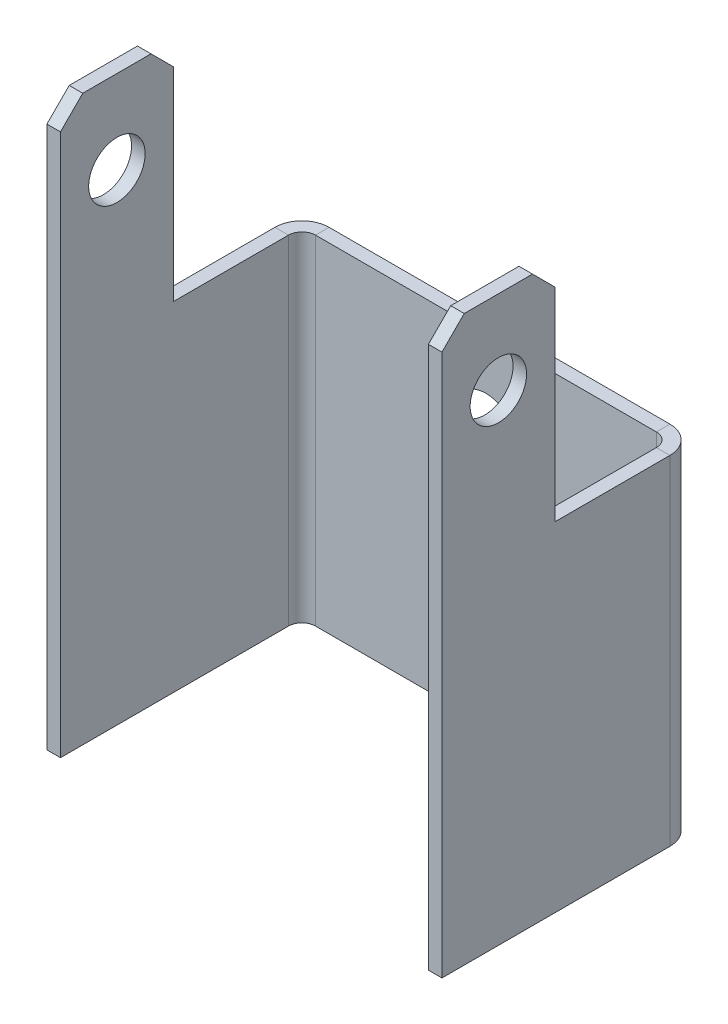
SolidWorks part; units mm, degrees
note: The reader was unsure of these and kept them because the rebuilt part matched: flange length of "Brida de arista1".
ref_plane "Alzado" through (0, 0, 0) normal (0, 0, 1) x (1, 0, 0)
ref_plane "Planta" through (0, 0, 0) normal (0, 1, 0) x (1, 0, 0)
ref_plane "Vista lateral" through (0, 0, 0) normal (1, 0, 0) x (0, 0, -1)
sketch "Croquis1" plane through (0, 0, 0) normal (0, 0, 1) x (1, 0, 0)
  line L1 (-22.225, 31.75) -> (22.225, 31.75)
  line L2 (-22.225, 31.75) -> (-22.225, -31.75)
  line L3 (-22.225, -31.75) -> (22.225, -31.75)
  line L4 (22.225, 31.75) -> (22.225, -31.75)
  line L5 (-22.225, 31.75) -> (22.225, -31.75) construction
  line L6 (-22.225, -31.75) -> (22.225, 31.75) construction
  point P0 (0, 0)
  dimension "D1" = 63.5
  dimension "D2" = 44.45
base flange "Brida base1" sketch "Croquis1" thickness 1.524 reverse thickness direction no parameters "D1"=0.508
edge flange "Brida de arista1" sketch "Croquis10" flange profiles "Croquis10", "Croquis11" flange angle 90 flange length 28.702 flange position material inside bend radius 1.524 thickness 1.524 relief rectangular parameters "D6"=10, "D8"=1
sketch "Croquis10" plane through (22.225, 0, 0) normal (-1, 0, 0) x (0, -1, 0)
  line L2 (-31.75, 0) -> (-31.75, 27.178)
  line L3 (-31.75, 27.178) -> (31.75, 27.178)
  line L4 (31.75, 27.178) -> (31.75, 0)
  line L5 (31.75, 0) -> (-31.75, 0) construction
  line L6 (31.75, 0) -> (-31.75, 0)
sketch "Croquis11" plane through (-22.225, 0, 0) normal (1, 0, 0) x (0, 1, 0)
  line L0 (31.75, 0) -> (-31.75, 0) construction
  line L1 (31.75, 0) -> (-31.75, 0)
  line L2 (31.75, 0) -> (31.75, 27.178)
  line L3 (31.75, 27.178) -> (-31.75, 27.178)
  line L4 (-31.75, 27.178) -> (-31.75, 0)
bend "Pliegue de arista1" bend radius 1.524 bend angle 90 parameters "D5"=1
bend "Pliegue de arista2" bend radius 1.524 bend angle 90 parameters "D5"=2
sketch "Croquis12" plane through (22.225, 0, 0) normal (1, 0, 0) x (0, 0, -1)
  line L0 (-14.478, 31.75) -> (-14.478, 6.35)
  line L4 (-27.178, 31.75) -> (-1.524, 31.75) construction
  line L6 (1.524, 6.35) -> (-14.478, 6.35)
  line L7 (1.524, 31.75) -> (1.524, -31.75) construction
  line L8 (-1.524, -31.75) -> (-27.178, -31.75) construction
  line L11 (1.524, 31.75) -> (-14.478, 31.75)
  line L12 (-27.178, -31.75) -> (-27.178, 31.75) construction
  line L13 (1.524, 6.35) -> (1.524, 31.75)
  circle A0 centre (-20.828, 22.352) radius 3.175
  dimension "D4" = 6.35
  dimension "D1" = 12.7
  dimension "D2" = 6.35
  dimension "1.5" = 38.1
  dimension "D3" = 54.102
extrude "Cortar-Extruir1" cut sketch "Croquis12" against normal blind 62.738 normal cut yes
sketch "Croquis13" plane through (0, 0, -1.524) normal (0, 0, -1) x (-1, 0, 0)
  line L0 (19.177, -31.75) -> (-19.177, -31.75) construction
  line L1 (-22.225, -31.75) -> (-22.225, 6.35) construction
  circle A0 centre (0, -22.098) radius 3.5687
  circle A1 centre (0, -3.048) radius 3.5687
  dimension "D3" = 7.1374
  dimension "D5" = 7.1374
  dimension "D1" = 9.652
  dimension "D2" = 22.225
  dimension "D4" = 19.05
  dimension "D6" = 22.225
extrude "Cortar-Extruir2" cut sketch "Croquis13" against normal blind 62.738 normal cut yes
sketch "Croquis14" plane through (22.225, 0, 0) normal (1, 0, 0) x (0, 0, -1)
  line L0 (-14.478, 31.75) -> (-16.9869, 31.75)
  line L1 (-27.178, 31.75) -> (-14.478, 31.75) construction
  line L2 (-14.478, 31.75) -> (-14.478, 29.2411)
  line L3 (-14.478, 31.75) -> (-14.478, 6.35) construction
  line L4 (-14.478, 29.2411) -> (-16.9869, 31.75)
  line L5 (-27.178, 31.75) -> (-24.6691, 31.75)
  line L6 (-27.178, 31.75) -> (-27.178, 29.2411)
  line L7 (-27.178, -31.75) -> (-27.178, 31.75) construction
  line L8 (-27.178, 29.2411) -> (-24.6691, 31.75)
  dimension "D1" = 45
  dimension "D2" = 45
extrude "Cortar-Extruir3" cut sketch "Croquis14" against normal blind 62.738 normal cut yes
sketch "Líneas de pliegue1" [suppressed] plane through (0, 0, 0) normal (0, 1, 0) x (1, 0, 0)
sketch "Cuadro delimitador1" [suppressed] plane through (0, 0, 0) normal (0, 1, 0) x (1, 0, 0)
sheet metal parameters "Chapa metálica1" thickness 1.524 parameters "D1"=0.508
flat pattern "Chapa desplegada1" [suppressed]
sketch "Líneas de pliegue2" plane through (0, 0, 0) normal (0, 1, 0) x (1, 0, 0)
sketch3d "Cuadro delimitador2" [suppressed]
  line L0 (-22.225, 31.75, 0) -> (-22.225, -31.75, 0) construction
  line L1 (22.225, 31.75, 0) -> (22.225, -31.75, 0) construction
  line L2 (-22.225, 31.75, 0) -> (22.225, 31.75, 0) construction
  line L3 (-22.225, -31.75, 0) -> (22.225, -31.75, 0) construction
sheet metal parameters "Chapa metálica2" thickness 1.524 parameters "D1"=0.508
flat pattern "Chapa desplegada1"
sketch "Líneas de pliegue2" plane through (0, 0, 0) normal (0, 0, 1) x (1, 0, 0)
  line L0 (-20.9485, 31.75) -> (-20.9485, -31.75) construction
  line L1 (20.9485, -31.75) -> (20.9485, 31.75) construction
  line L2 (-20.9485, 31.75) -> (-20.9485, -31.75) construction
  line L3 (20.9485, -31.75) -> (20.9485, 31.75) construction
sketch3d "Cuadro delimitador2" [suppressed]
  line L0 (-48.374, -31.75, 0) -> (48.374, -31.75, 0) construction
  line L1 (-48.374, 31.75, 0) -> (48.374, 31.75, 0) construction
  line L2 (-48.374, -31.75, 0) -> (-48.374, 31.75, 0) construction
  line L3 (48.374, -31.75, 0) -> (48.374, 31.75, 0) construction
bend of the flat pattern "Aplanar-<Pliegue de arista1>1"
bend of the flat pattern "Aplanar-<Pliegue de arista2>1"
sheet metal parameters "Chapa metálica3" thickness 1.524 parameters "D1"=0.508
flat pattern "Chapa desplegada1"
sketch "Líneas de pliegue2" plane through (0, 0, 0) normal (0, 0, 1) x (1, 0, 0)
  line L0 (-20.9485, 6.35) -> (-20.9485, -31.75) construction
  line L1 (20.9485, -31.75) -> (20.9485, 6.35) construction
  line L2 (-20.9485, 6.35) -> (-20.9485, -31.75) construction
  line L3 (20.9485, -31.75) -> (20.9485, 6.35) construction
sketch3d "Cuadro delimitador2" [suppressed]
  line L0 (-48.374, -31.75, 0) -> (48.374, -31.75, 0) construction
  line L1 (-48.374, 31.75, 0) -> (48.374, 31.75, 0) construction
  line L2 (-48.374, -31.75, 0) -> (-48.374, 31.75, 0) construction
  line L3 (48.374, -31.75, 0) -> (48.374, 31.75, 0) construction
bend of the flat pattern "Aplanar-<Pliegue de arista1>1"
bend of the flat pattern "Aplanar-<Pliegue de arista2>1"
sheet metal parameters "Chapa metálica4" thickness 1.524 parameters "D1"=0.508
flat pattern "Chapa desplegada1"
sketch "Líneas de pliegue2" plane through (0, 0, 0) normal (0, 0, 1) x (1, 0, 0)
  line L0 (-20.9485, 6.35) -> (-20.9485, -31.75) construction
  line L1 (20.9485, -31.75) -> (20.9485, 6.35) construction
  line L2 (-20.9485, 6.35) -> (-20.9485, -31.75) construction
  line L3 (20.9485, -31.75) -> (20.9485, 6.35) construction
sketch3d "Cuadro delimitador2" [suppressed]
  line L0 (-48.374, -31.75, 0) -> (48.374, -31.75, 0) construction
  line L1 (-48.374, 31.75, 0) -> (48.374, 31.75, 0) construction
  line L2 (-48.374, -31.75, 0) -> (-48.374, 31.75, 0) construction
  line L3 (48.374, -31.75, 0) -> (48.374, 31.75, 0) construction
bend of the flat pattern "Aplanar-<Pliegue de arista1>1"
bend of the flat pattern "Aplanar-<Pliegue de arista2>1"
sheet metal parameters "Chapa metálica5" thickness 1.524 parameters "D1"=0.508
flat pattern "Chapa desplegada1"
sketch "Líneas de pliegue2" plane through (0, 0, 0) normal (0, 0, 1) x (1, 0, 0)
  line L0 (-20.9485, 6.35) -> (-20.9485, -31.75) construction
  line L1 (20.9485, -31.75) -> (20.9485, 6.35) construction
  line L2 (-20.9485, 6.35) -> (-20.9485, -31.75) construction
  line L3 (20.9485, -31.75) -> (20.9485, 6.35) construction
sketch3d "Cuadro delimitador2" [suppressed]
  line L0 (-48.374, -31.75, 0) -> (48.374, -31.75, 0) construction
  line L1 (-48.374, 31.75, 0) -> (48.374, 31.75, 0) construction
  line L2 (-48.374, -31.75, 0) -> (-48.374, 31.75, 0) construction
  line L3 (48.374, -31.75, 0) -> (48.374, 31.75, 0) construction
bend of the flat pattern "Aplanar-<Pliegue de arista1>1"
bend of the flat pattern "Aplanar-<Pliegue de arista2>1"
